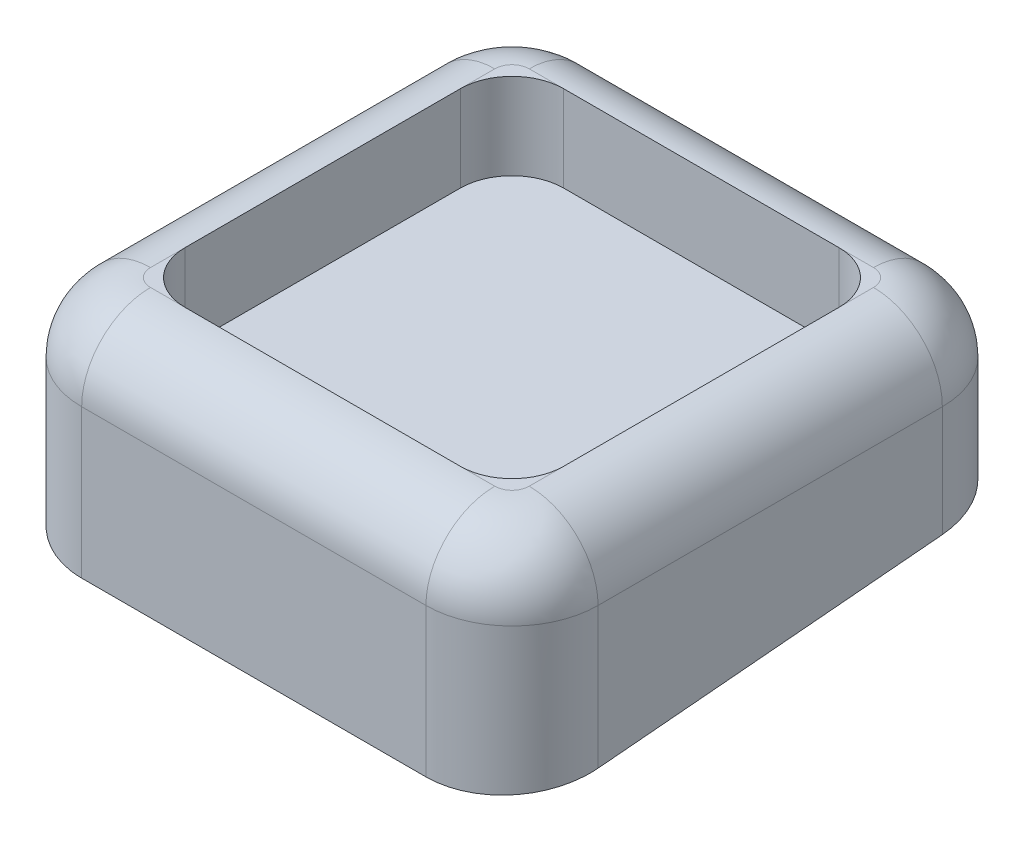
SolidWorks part; units mm, degrees
ref_plane "Front Plane" through (0, 0, 0) normal (0, 0, 1) x (1, 0, 0)
ref_plane "Top Plane" through (0, 0, 0) normal (0, 1, 0) x (1, 0, 0)
ref_plane "Right Plane" through (0, 0, 0) normal (1, 0, 0) x (0, 0, -1)
sketch "Sketch1" plane through (0, 0, 0) normal (1, 0, 0) x (0, 0, -1)
  line L0 (-15, -5) -> (-15, -7.625)
  line L1 (-15, -5) -> (15, -5)
  line L2 (-15, -5) -> (-15, 5)
  line L3 (-15, 5) -> (15, 5)
  line L4 (15, -5) -> (15, 5)
  line L5 (-15, -5) -> (15, 5) construction
  line L6 (-15, 5) -> (15, -5) construction
  line L7 (-15, -7.625) -> (15, -5)
  point P1 (0, 0)
  dimension "D1" = 30
  dimension "D2" = 10
  dimension "D3" = 2.625
extrude "Boss-Extrude1" add sketch "Sketch1" along normal blind 30 contours L0 L7 L1 | L1 L4 L3 L2 region at (0, -5.875, 5) region at (0, 0, 0)
sketch "Sketch2" plane through (0, 5, 0) normal (0, 1, 0) x (1, 0, 0)
  line L0 (0, -15) -> (0, 15) construction
  line L1 (30, 15) -> (0, 15) construction
  line L2 (30, -15) -> (30, 15) construction
  line L3 (30, -15) -> (0, -15) construction
  line L4 (0, -15) -> (0, 15) construction
  line L5 (30, 15) -> (0, 15) construction
  line L6 (30, -15) -> (30, 15) construction
  line L7 (30, -15) -> (0, -15) construction
  line L8 (26, -11) -> (26, 11)
  line L9 (26, 11) -> (4, 11)
  line L10 (4, -11) -> (4, 11)
  line L11 (26, -11) -> (4, -11)
  dimension "D1" = 4
extrude "Cut-Extrude1" cut sketch "Sketch2" against normal blind 5
fillet "Fillet1" radius 5 4 edges at (0, -1.3125, 15) (0, 0, -15) (30, 0, -15) (30, -1.3125, 15)
fillet "Fillet2" radius 3 4 edges at (4, 2.5, -11) (4, 2.5, 11) (26, 2.5, 11) (26, 2.5, -11)
fillet "Fillet3" radius 4 8 edges at (28.5355, 5, -13.5355) (30, 5, 0) (28.5355, 5, 13.5355) (15, 5, 15) (1.4645, 5, 13.5355) (0, 5, 0) (1.4645, 5, -13.5355) (15, 5, -15)
